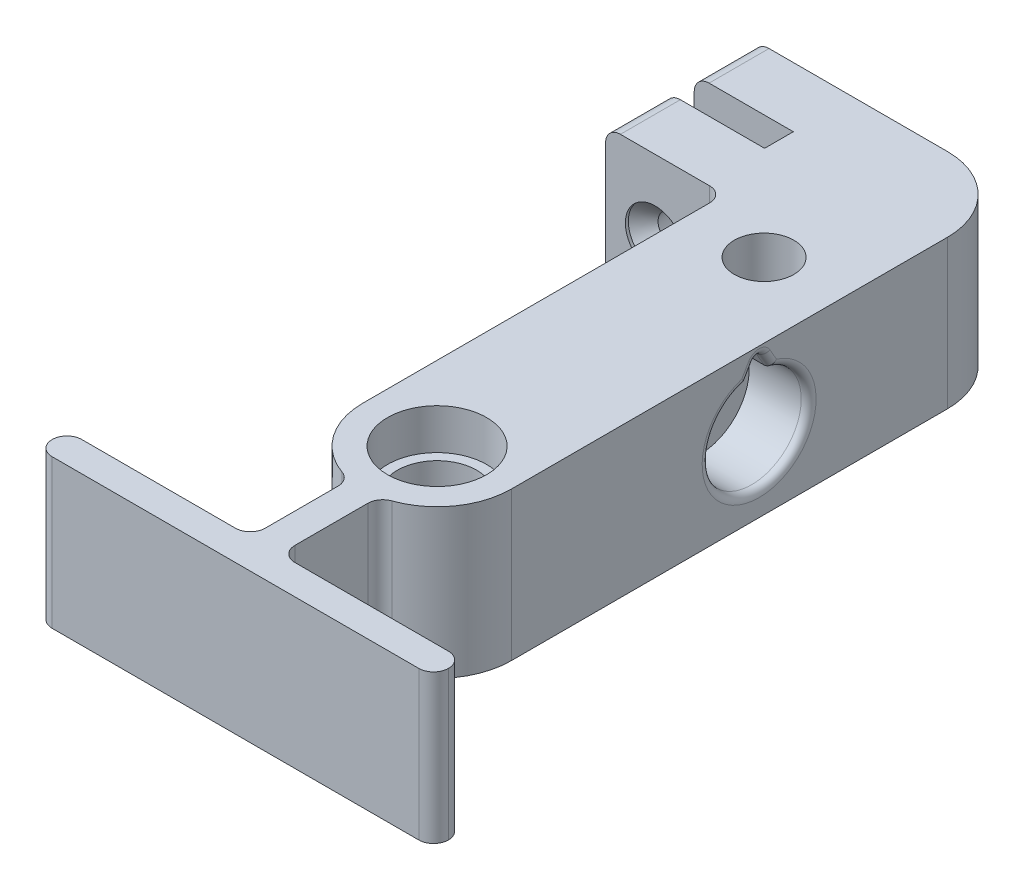
SolidWorks part; units mm, degrees
ref_plane "Front Plane" through (0, 0, 0) normal (0, 0, 1) x (1, 0, 0)
ref_plane "Top Plane" through (0, 0, 0) normal (0, 1, 0) x (1, 0, 0)
ref_plane "Right Plane" through (0, 0, 0) normal (1, 0, 0) x (0, 0, -1)
sketch "Sketch1" plane through (0, 0, 0) normal (0, 1, 0) x (1, 0, 0)
  line L0 (0, 22) -> (0, -22) construction
  line L1 (-7.5, 22) -> (7.5, 22)
  line L2 (-7.5, 22) -> (-7.5, -22)
  line L3 (-7.5, -22) -> (7.5, -22)
  line L4 (7.5, 22) -> (7.5, -22)
  line L5 (-7.5, 22) -> (7.5, -22) construction
  line L6 (-7.5, -22) -> (7.5, 22) construction
  circle A0 centre (0, -14.5) radius 4
  circle A1 centre (0, -14.5) radius 7.5
  point P0 (0, 0)
  dimension "D1" = 8
  dimension "D2" = 15
  dimension "D4" = 44
extrude "Boss-Extrude1" add sketch "Sketch1" along normal mid plane 15 contours L2 | L4 | A1 L4 L1 L2 | A1 A0 | L3 region at (0, 0, -6.6495) region at (0, 0, 7.2121)
sketch "Sketch2" plane through (0, 7.5, 0) normal (0, 1, 0) x (1, 0, 0)
  circle A0 centre (0, -14.5) radius 5
  dimension "D1" = 10
extrude "Cut-Extrude1" cut sketch "Sketch2" against normal blind 4.1
mirror "Mirror1" about plane through (0, 0, 0) normal (0, 1, 0) of "Cut-Extrude1"
sketch "Sketch12" plane through (0, -3.4, 0) normal (0, -1, 0) x (1, 0, 0)
  circle A0 centre (0, 14.5) radius 4 construction
  circle A1 centre (0, 14.5) radius 5
  circle A2 centre (0, 14.5) radius 5
  circle A3 centre (0, 14.5) radius 4
  dimension "D1" = 0
extrude "Cut-Extrude10" cut sketch "Sketch12" against normal blind 1
sketch "Sketch4" plane through (7.5, 0, 0) normal (1, 0, 0) x (0, 0, -1)
  line L0 (-3.1918, 0) -> (3.917, 0) construction
  line L1 (9.25, 4.8412) -> (11.75, 4.8412) construction
  line L2 (-9.5, 7.5) -> (-19.5, 7.5) construction
  line L3 (-9.5, 7.5) -> (-19.5, 7.5)
  line L4 (-14.5, 7.5) -> (-14.5, -7.5) construction
  line L5 (22, -7.5) -> (-14.5, -7.5) construction
  line L6 (10.5, 0) -> (10.5, 7.5) construction
  line L9 (22, 7.5) -> (-14.5, 7.5) construction
  line L10 (10.5, 7.0063) -> (9.25, 4.8412)
  line L11 (10.5, 7.0063) -> (11.75, 4.8412)
  circle A1 centre (10.5, 0) radius 5
  circle A3 centre (10.5, 6.0063) radius 0.5
  dimension "D1" = 25
  dimension "D2" = 10
  dimension "D5" = 1
  dimension "D4" = 2.5
extrude "Cut-Extrude3" cut sketch "Sketch4" against normal blind 6 contours A1 | A1 L11 L10 | A3 region at (7.5, 5.3219, -10.5) region at (7.5, 6.0063, -10.5) region at (7.5, 0, -10.5)
mirror "Mirror2" about plane through (0, 0, 0) normal (1, 0, 0) of "Cut-Extrude3"
sketch "Sketch18" plane through (0, -7.5, 0) normal (0, -1, 0) x (1, 0, 0)
  line L0 (0, -41.3409) -> (0, 22.3101) construction
  line L4 (7.5, -3.75) -> (-7.5, -3.75) construction
  line L5 (-19.5, -22) -> (-7.5, -22)
  line L6 (7.5, -29.5) -> (7.5, -22)
  line L7 (7.5, -22) -> (7.5, 14.5) construction
  line L8 (-7.5, -22) -> (7.5, -22)
  line L9 (-7.5, -22) -> (-7.5, 14.5) construction
  line L10 (0, -22) -> (0, -37) construction
  line L11 (0, -37) -> (-19.5, -37)
  line L13 (-19.5, -22) -> (-19.5, -37)
  circle A1 centre (0, -29.5) radius 7.5
  line M10 (-7.5, -22) -> (7.5, -22)
  dimension "D1" = 12
extrude "Boss-Extrude3" add sketch "Sketch18" against normal up to surface (15 mm away) contours A1 L6 L8 | A1 M10 | A1 | A1 L13 L11 region at (-12.5923, -7.5, -29.5) region at (5.8247, -7.5, -23.6753) region at (0, -7.5, -29.5) up to face at (0, 7.5, 19.5)
sketch "Sketch7" plane through (0, 7.5, 0) normal (0, 1, 0) x (1, 0, 0)
  line L0 (-19.5, 29.5) -> (7.5, 29.5) construction
  line L8 (7.5, 29.5) -> (7.5, -14.5) construction
  line L9 (-19.5, 28.05) -> (-9.5, 28.05)
  line L10 (-19.5, 28.05) -> (-19.5, 30.95)
  line L11 (-9.5, 28.05) -> (-9.5, 30.95)
  line L12 (-19.5, 30.95) -> (-9.5, 30.95)
  line L13 (-19.5, 28.05) -> (-9.5, 30.95) construction
  line L14 (-9.5, 28.05) -> (-19.5, 30.95) construction
  line L15 (-19.5, 22) -> (-19.5, 37) construction
  point P8 (-14.5, 29.5)
  dimension "D1" = 10
  dimension "D2" = 2.9
extrude "Cut-Extrude7" cut sketch "Sketch7" against normal up to next
sketch "Sketch8" plane through (-40.2452, 0, -37) normal (0, 0, 1) x (1, 0, 0)
  line L5 (20.7452, 0) -> (40.2452, 0) construction
  line L8 (20.7452, 7.5) -> (20.7452, -7.5) construction
  line L9 (40.2452, 7.5) -> (40.2452, -7.5) construction
  circle A2 centre (25.7452, 0) radius 1.5
  dimension "D2" = 5
  dimension "D3" = 3
extrude "Cut-Extrude8" cut sketch "Sketch8" along normal up to surface (15 mm away) contours A2 up to face at (-13.5, 0, -22)
hole_wizard "CSK for M3 Flat Head Machine Screw1" positions "Sketch9" profile "Sketch10" countersink size "M3" standard "ANSI Metric"
sketch "Sketch9" plane through (-83.1458, 0, -22) normal (0, 0, 1) x (1, 0, 0)
  point P6 (68.6458, 0)
  point P17 (0, 0)
  point P18 (0, 0)
  point P19 (0, 0)
  point P20 (0, 0)
sketch "Sketch10" plane through (-14.5, 0, -22) normal (1, 0, 0) x (0, -1, 0)
  line L0 (0, 0) -> (0, 5.9013)
  line L1 (0, 5.9013) -> (1.5, 5)
  line L2 (1.5, 5) -> (1.5, 1.8)
  line L3 (1.5, 1.8) -> (3, 0.3)
  line L4 (3, 0.3) -> (3, 0)
  line L6 (3, 0) -> (0, 0)
  line L7 (-1.5, 1.8) -> (-3, 0.3) construction
  line L10 (0, 5.9013) -> (-1.5, 5) construction
  line L11 (0, -6.35) -> (0, 107.95) construction
  dimension "Hole Dia." = 3
  dimension "Hole Depth" = 5
  dimension "C'Sink Dia." = 6
  dimension "C'Sink Angle" = 90
  dimension "Drill Angle" = 118
  dimension "Head Clearance" = 0.3
sketch "Sketch11" plane through (15, 0, -37) normal (0, 0, 1) x (1, 0, 0)
  line L7 (-34.5, 7.5) -> (-34.5, -7.5) construction
  line L8 (-29.5, -3.4641) -> (-26.5, -1.7321)
  line L15 (-26.5, -1.7321) -> (-26.5, 1.7321)
  line L16 (-26.5, 1.7321) -> (-29.5, 3.4641)
  line L17 (-29.5, 3.4641) -> (-32.5, 1.7321)
  line L18 (-32.5, 1.7321) -> (-32.5, -1.7321)
  line L19 (-32.5, -1.7321) -> (-29.5, -3.4641)
  circle A0 centre (-29.5, 0) radius 3 construction
  dimension "D1" = 6
extrude "Cut-Extrude9" cut sketch "Sketch11" along normal blind 3
sketch "Sketch13" plane through (-44.6536, 0, -30.95) normal (0, 0, 1) x (1, 0, 0)
  line L0 (35.1536, -7.5) -> (35.1536, 7.5) construction
  line L2 (35.1536, -7.5) -> (35.1536, 7.5)
  line L3 (35.1536, 0) -> (44.6536, 0) construction
  line L4 (44.6536, 7.5) -> (44.6536, -7.5) construction
  line L5 (35.1536, 7.5) -> (42.6536, 0)
  line L6 (35.1536, -7.5) -> (42.6536, 0)
  dimension "D1" = 45
extrude "Cut-Extrude11" cut sketch "Sketch13" along normal up to surface (2.9 mm away) contours L5 L6 L2 up to face at (-13, 0, -28.05)
sketch "Sketch16" plane through (0, -7.5, 0) normal (0, -1, 0) x (1, 0, 0)
  line L0 (0, 42.718) -> (0, -5.4521) construction
  line L2 (-1.5, 31.8485) -> (1.5, 31.8485)
  line L3 (-1.5, 31.8485) -> (-1.5, 21.8485)
  line L4 (-1.5, 21.8485) -> (1.5, 21.8485)
  line L5 (1.5, 31.8485) -> (1.5, 21.8485)
  line L6 (-1.5, 31.8485) -> (1.5, 21.8485) construction
  line L7 (-1.5, 21.8485) -> (1.5, 31.8485) construction
  line L8 (-20, 34.8485) -> (20, 34.8485)
  line L9 (-20, 34.8485) -> (-20, 31.8485)
  line L10 (-20, 31.8485) -> (20, 31.8485)
  line L11 (20, 34.8485) -> (20, 31.8485)
  line L12 (-20, 34.8485) -> (20, 31.8485) construction
  line L13 (-20, 31.8485) -> (20, 34.8485) construction
  arc A0 (7.5, 14.5) -> (-7.5, 14.5) centre (0, 14.5) ccw construction
  point P1 (0, 26.8485)
  point P11 (0, 33.3485)
  arc M14 (7.5, 14.5) -> (-7.5, 14.5) centre (0, 14.5) ccw
  dimension "D1" = 3
  dimension "D2" = 10
  dimension "D3" = 40
extrude "Boss-Extrude2" add sketch "Sketch16" against normal up to surface (15 mm away) contours L5 L2 L3 M14 | L11 L8 L9 L10 L2 region at (0, -7.5, 33.3485) region at (0, -7.5, 26.899) up to face at (-8.677, 7.5, -20.9594)
fillet "Fillet8" radius 1.5 14 edges at (20, 0, 31.8485) (20, 0, 34.8485) (-20, 0, 34.8485) (-20, 0, 31.8485) (-1.5, 0, 31.8485) (-1.5, 0, 21.8485) (1.5, 0, 21.8485) (1.5, 0, 31.8485) (-19.5, -7.5, -25.025) (-19.5, -7.5, -33.975) (-19.5, 7.5, -33.975) (-19.5, 7.5, -25.025) (-7.5, 0, -22) (-2, 0, -29.5)
sketch "Sketch19" plane through (0, -7.5, 0) normal (0, -1, 0) x (1, 0, 0)
  line L0 (0, 4.3088) -> (0, -5.4508) construction
  circle A0 centre (0, -18.5) radius 3
  circle A2 centre (0, 14.5) radius 5 construction
  dimension "D1" = 6
  dimension "D2" = 33
extrude "Cut-Extrude12" cut sketch "Sketch19" against normal up to next contours A0
fillet "Fillet9" radius 0.75 8 edges at (-7.5, 5.5488, -11.3415) (-7.5, 6.5063, -10.5) (7.5, 5.5488, -9.6585) (7.5, 6.5063, -10.5) (-7.5, 5.5488, -9.6585) (-7.5, -5, -10.5) (7.5, 5.5488, -11.3415) (7.5, -5, -10.5)
